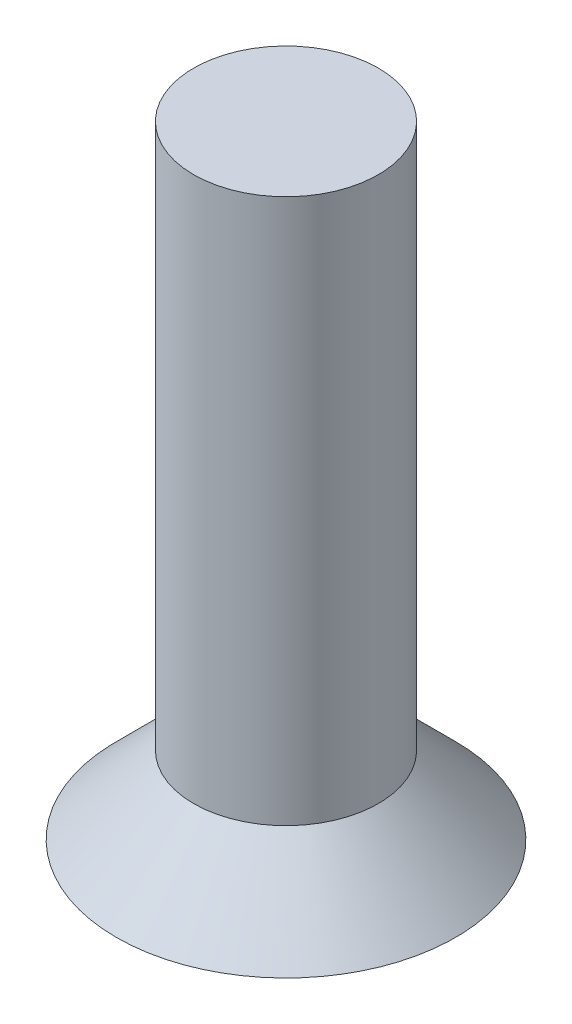
SolidWorks part; units mm, degrees
material "Plain Carbon Steel"
ref_plane "Front Plane" through (0, 0, 0) normal (0, 0, 1) x (1, 0, 0)
ref_plane "Top Plane" through (0, 0, 0) normal (0, 1, 0) x (1, 0, 0)
ref_plane "Right Plane" through (0, 0, 0) normal (1, 0, 0) x (0, 0, -1)
sketch "Sketch1" plane through (0, 0, 0) normal (0, 1, 0) x (1, 0, 0)
  circle A0 centre (0, 0) radius 4.5
  dimension "D1" = 9
extrude "Boss-Extrude1" add sketch "Sketch1" along normal blind 2.5
sketch "Sketch2" plane through (0, 2.5, 0) normal (0, 1, 0) x (1, 0, 0)
  circle A0 centre (0, 0) radius 2.45
  dimension "D1" = 4.9
extrude "Boss-Extrude2" add sketch "Sketch2" along normal blind 14
chamfer "Chamfer1" distance 2.5 angle 45 1 edges at (0, 2.5, 4.5)
sketch "Sketch3" plane through (0, 0, 0) normal (0, -1, 0) x (1, 0, 0)
  line L1 (0, -1.6625) -> (1.4397, -0.8312)
  line L2 (1.4397, -0.8312) -> (1.4397, 0.8312)
  line L3 (1.4397, 0.8312) -> (0, 1.6625)
  line L4 (0, 1.6625) -> (-1.4397, 0.8312)
  line L5 (-1.4397, 0.8312) -> (-1.4397, -0.8312)
  line L6 (-1.4397, -0.8312) -> (0, -1.6625)
  circle A0 centre (0, 0) radius 1.4397 construction
extrude "Cut-Extrude1" cut sketch "Sketch3" against normal blind 1.5
